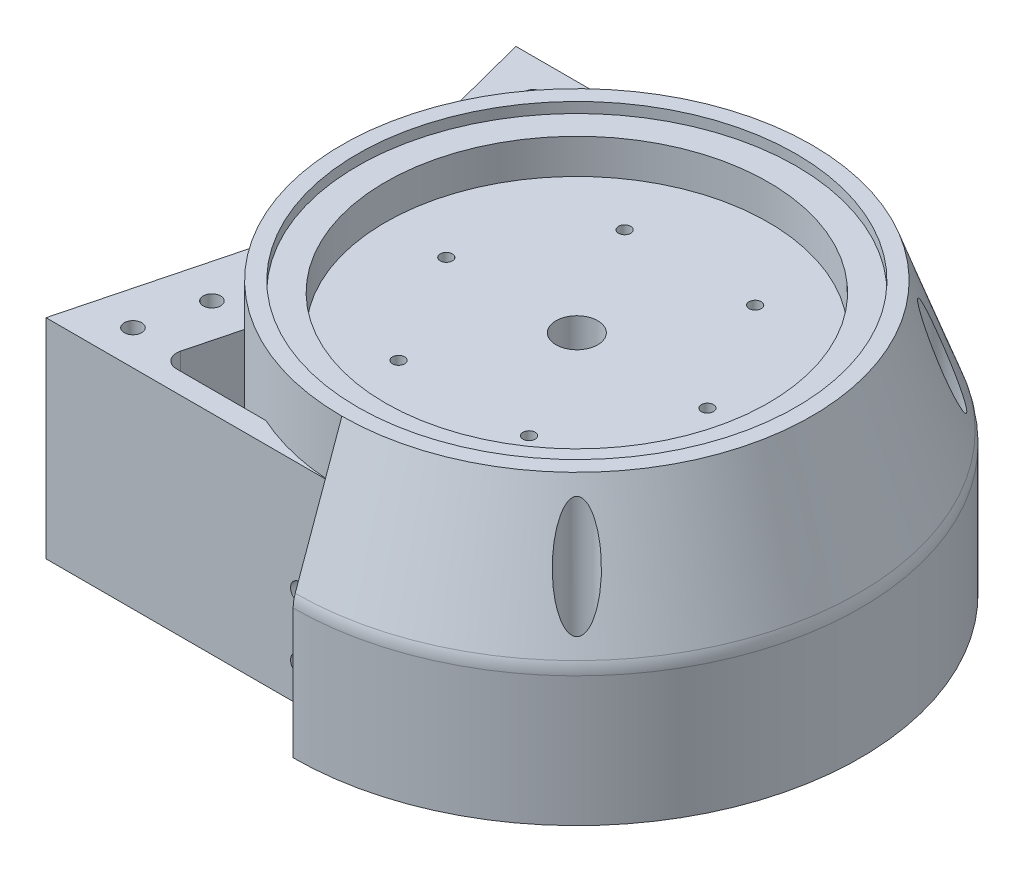
SolidWorks part; units mm, degrees
ref_plane "Alzado" through (0, 0, 0) normal (0, 0, 1) x (1, 0, 0)
ref_plane "Planta" through (0, 0, 0) normal (0, 1, 0) x (1, 0, 0)
ref_plane "Vista lateral" through (0, 0, 0) normal (1, 0, 0) x (0, 0, -1)
sketch "Croquis1" plane through (0, 0, 0) normal (0, 1, 0) x (1, 0, 0)
  line L0 (-55, 0) -> (55, 0) construction
  line L1 (-158, 67.5) -> (0, 67.5)
  line L2 (-158, 67.5) -> (-158, -67.5)
  line L3 (-158, -67.5) -> (0, -67.5)
  line L5 (-158, 67.5) -> (0, -67.5) construction
  line L6 (-158, -67.5) -> (0, 67.5) construction
  line L8 (-58.5, 0) -> (-48.5, 0) construction
  line L9 (-58.5, 0) -> (-48.5, 0) construction
  line L10 (-150, 59.5) -> (-93, 59.5) construction
  line L11 (-150, 59.5) -> (-150, 2.5) construction
  line L12 (-150, 2.5) -> (-93, 2.5) construction
  line L13 (-93, 59.5) -> (-93, 2.5) construction
  arc A0 (0, -67.5) -> (0, 67.5) centre (0, 0) ccw
  circle A1 centre (0, 0) radius 48.5 construction
  circle A2 centre (-71, 0) radius 12.5 construction
  point P4 (-79, 0)
  dimension "D1" = 135
  dimension "D2" = 97
  dimension "D3" = 25
  dimension "D4" = 10
  dimension "D5" = 8
  dimension "D6" = 57
  dimension "D7" = 8
  dimension "D8" = 158
extrude "Saliente-Extruir1" add sketch "Croquis1" along normal blind 110
sketch "Croquis2" plane through (0, 110, 0) normal (0, 1, 0) x (1, 0, 0)
  line L0 (-158, 67.5) -> (-158, -67.5) construction
  line L1 (-140, 59.5) -> (-103, 59.5)
  line L2 (-150, 49.5) -> (-150, 12.5)
  line L3 (-150, 12.5) -> (-140, 12.5)
  line L4 (-93, 49.5) -> (-93, 12.5)
  line L5 (0, 67.5) -> (-158, 67.5) construction
  line L6 (-150, 49.5) -> (-140, 49.5)
  line L7 (-140, 49.5) -> (-140, 59.5)
  line L8 (-121.5, 59.5) -> (-121.5, 2.5) construction
  line L9 (-150, 31) -> (-93, 31) construction
  line L10 (-103, 49.5) -> (-103, 59.5)
  line L11 (-93, 49.5) -> (-103, 49.5)
  line L12 (-93, 12.5) -> (-103, 12.5)
  line L13 (-103, 12.5) -> (-103, 2.5)
  line L14 (-140, 12.5) -> (-140, 2.5)
  line L16 (-140, 2.5) -> (-103, 2.5)
  point P13 (-121.5, 31)
  dimension "D1" = 8
  dimension "D2" = 8
  dimension "D3" = 37
  dimension "D4" = 37
  dimension "D5" = 57
extrude "Cortar-Extruir1" cut sketch "Croquis2" against normal blind 102
fillet "Redondeo1" radius 2 8 edges at (-150, 59, -49.5) (-150, 59, -12.5) (-140, 59, -2.5) (-103, 59, -2.5) (-93, 59, -12.5) (-93, 59, -49.5) (-103, 59, -59.5) (-140, 59, -59.5)
fillet "Redondeo2" radius 5 4 edges at (-103, 59, -12.5) (-140, 59, -12.5) (-103, 59, -49.5) (-140, 59, -49.5)
sketch "Croquis3" plane through (0, 110, 0) normal (0, 1, 0) x (1, 0, 0)
  line L0 (-150, 47.5) -> (-150, 14.5) construction
  line L1 (-150, 2.5) -> (-93, 2.5)
  line L2 (-150, 2.5) -> (-150, 59.5)
  line L3 (-150, 59.5) -> (-93, 59.5)
  line L4 (-93, 2.5) -> (-93, 59.5)
  line L5 (-138, 2.5) -> (-105, 2.5) construction
  line L6 (-105, 59.5) -> (-138, 59.5) construction
  line L7 (-93, 14.5) -> (-93, 47.5) construction
extrude "Cortar-Extruir2" cut sketch "Croquis3" against normal blind 5
sketch "Croquis4" plane through (0, 110, 0) normal (0, 1, 0) x (1, 0, 0)
  circle A0 centre (0, 0) radius 6
  dimension "D1" = 12
extrude "Cortar-Extruir3" cut sketch "Croquis4" against normal blind 100
sketch "Croquis5" plane through (0, 110, 0) normal (0, 1, 0) x (1, 0, 0)
  line L0 (-60.5, 0) -> (60.5, 0) construction
  line L1 (-89, -1000) -> (-89, 49000) construction
  line L2 (-93, 14.5) -> (-93, 47.5) construction
  circle A1 centre (-76.5, 0) radius 12.5 construction
  circle A2 centre (-76.5, 0) radius 3
  circle A3 centre (0, 0) radius 62 construction
  dimension "D1" = 124
  dimension "D2" = 25
  dimension "D4" = 6
  dimension "D3" = 4
extrude "Cortar-Extruir4" cut sketch "Croquis5" against normal blind 100
sketch "Croquis6" plane through (0, 110, 0) normal (0, 1, 0) x (1, 0, 0)
  line L0 (-68.1506, 2.5096) -> (-85, 67.5)
  line L1 (0, 67.5) -> (-158, 67.5) construction
  line L2 (-85, 67.5) -> (0, 67.5)
  line L3 (-60.5, 0) -> (60.5, 0) construction
  line L4 (-85, -67.5) -> (0, -67.5)
  line L5 (-68.1506, -2.5096) -> (-85, -67.5)
  line L6 (-93, 2.5) -> (-93, 59.5) construction
  arc A0 (0, -67.5) -> (0, 67.5) centre (0, 0) ccw
  arc A1 (0, -67.5) -> (0, 67.5) centre (0, 0) ccw construction
  arc A2 (-68.1506, 2.5096) -> (-68.1506, -2.5096) centre (-77.8306, 0) cw
  point P20 (-67.5, 0)
  dimension "D2" = 10
  dimension "D1" = 8
extrude "Cortar-Extruir5" cut sketch "Croquis6" against normal blind 32
sketch "Croquis7" plane through (0, 110, 0) normal (0, 1, 0) x (1, 0, 0)
  line L0 (-70.8172, -12.7947) -> (-85, -67.5)
  line L1 (-68.1506, -2.5096) -> (-85, -67.5) construction
  line L2 (-85, -67.5) -> (-158, -67.5)
  line L3 (-93, 2.5) -> (-158, 2.5)
  line L4 (-158, 67.5) -> (-158, -67.5) construction
  line L5 (-158, 2.5) -> (-158, -67.5)
  line L6 (-138, 2.5) -> (-105, 2.5) construction
  line L7 (-93, 2.5) -> (-89.2537, -5.7744)
  arc A0 (-89.2537, -5.7744) -> (-70.8172, -12.7947) centre (-76.5, 0) ccw
  dimension "D1" = 28
extrude "Saliente-Extruir2" add sketch "Croquis7" along normal blind 23
sketch "Croquis8" plane through (0, 133, 0) normal (0, 1, 0) x (1, 0, 0)
  line L0 (-158, 0) -> (-93, 0) construction
  line L1 (-158, 2.5) -> (-158, -67.5) construction
  line L2 (-105, -59.5) -> (-138, -59.5)
  line L3 (-103, -54.5) -> (-103, -57.5)
  line L4 (-95, -49.5) -> (-98, -49.5)
  line L5 (-93, -14.5) -> (-93, -47.5)
  line L6 (-98, -12.5) -> (-95, -12.5)
  line L7 (-103, -4.5) -> (-103, -7.5)
  line L8 (-138, -2.5) -> (-105, -2.5)
  line L9 (-140, -7.5) -> (-140, -4.5)
  line L10 (-148, -12.5) -> (-145, -12.5)
  line L11 (-150, -47.5) -> (-150, -14.5)
  line L12 (-145, -49.5) -> (-148, -49.5)
  line L13 (-140, 57.5) -> (-140, 54.5)
  line L14 (-145, 49.5) -> (-148, 49.5)
  line L15 (-150, 47.5) -> (-150, 14.5)
  line L16 (-148, 12.5) -> (-145, 12.5)
  line L17 (-140, 7.5) -> (-140, 4.5)
  line L18 (-138, 2.5) -> (-105, 2.5)
  line L19 (-103, 4.5) -> (-103, 7.5)
  line L20 (-98, 12.5) -> (-95, 12.5)
  line L21 (-93, 14.5) -> (-93, 47.5)
  line L22 (-95, 49.5) -> (-98, 49.5)
  line L23 (-103, 54.5) -> (-103, 57.5)
  line L24 (-105, 59.5) -> (-138, 59.5)
  line L25 (-140, 57.5) -> (-140, 54.5) construction
  line L26 (-145, 49.5) -> (-148, 49.5) construction
  line L27 (-150, 47.5) -> (-150, 14.5) construction
  line L28 (-148, 12.5) -> (-145, 12.5) construction
  line L29 (-140, 7.5) -> (-140, 4.5) construction
  line L30 (-138, 2.5) -> (-105, 2.5) construction
  line L31 (-103, 4.5) -> (-103, 7.5) construction
  line L32 (-98, 12.5) -> (-95, 12.5) construction
  line L33 (-93, 14.5) -> (-93, 47.5) construction
  line L34 (-95, 49.5) -> (-98, 49.5) construction
  line L35 (-103, 54.5) -> (-103, 57.5) construction
  line L36 (-105, 59.5) -> (-138, 59.5) construction
  line L37 (-140, -57.5) -> (-140, -54.5)
  line L38 (-158, -67.5) -> (-85, -67.5) construction
  arc A0 (-138, -59.5) -> (-140, -57.5) centre (-138, -57.5) cw
  arc A1 (-103, -57.5) -> (-105, -59.5) centre (-105, -57.5) cw
  arc A2 (-103, -54.5) -> (-98, -49.5) centre (-98, -54.5) cw
  arc A3 (-93, -47.5) -> (-95, -49.5) centre (-95, -47.5) cw
  arc A4 (-95, -12.5) -> (-93, -14.5) centre (-95, -14.5) cw
  arc A5 (-98, -12.5) -> (-103, -7.5) centre (-98, -7.5) cw
  arc A6 (-105, -2.5) -> (-103, -4.5) centre (-105, -4.5) cw
  arc A7 (-140, -4.5) -> (-138, -2.5) centre (-138, -4.5) cw
  arc A8 (-140, -7.5) -> (-145, -12.5) centre (-145, -7.5) cw
  arc A9 (-150, -14.5) -> (-148, -12.5) centre (-148, -14.5) cw
  arc A10 (-148, -49.5) -> (-150, -47.5) centre (-148, -47.5) cw
  arc A11 (-145, -49.5) -> (-140, -54.5) centre (-145, -54.5) cw
  arc A12 (-145, 49.5) -> (-140, 54.5) centre (-145, 54.5) ccw
  arc A13 (-148, 49.5) -> (-150, 47.5) centre (-148, 47.5) ccw
  arc A14 (-150, 14.5) -> (-148, 12.5) centre (-148, 14.5) ccw
  arc A15 (-140, 7.5) -> (-145, 12.5) centre (-145, 7.5) ccw
  arc A16 (-140, 4.5) -> (-138, 2.5) centre (-138, 4.5) ccw
  arc A17 (-105, 2.5) -> (-103, 4.5) centre (-105, 4.5) ccw
  arc A18 (-98, 12.5) -> (-103, 7.5) centre (-98, 7.5) ccw
  arc A19 (-95, 12.5) -> (-93, 14.5) centre (-95, 14.5) ccw
  arc A20 (-93, 47.5) -> (-95, 49.5) centre (-95, 47.5) ccw
  arc A21 (-103, 54.5) -> (-98, 49.5) centre (-98, 54.5) ccw
  arc A22 (-103, 57.5) -> (-105, 59.5) centre (-105, 57.5) ccw
  arc A23 (-138, 59.5) -> (-140, 57.5) centre (-138, 57.5) ccw
  arc A24 (-145, 49.5) -> (-140, 54.5) centre (-145, 54.5) ccw construction
  arc A25 (-148, 49.5) -> (-150, 47.5) centre (-148, 47.5) ccw construction
  arc A26 (-150, 14.5) -> (-148, 12.5) centre (-148, 14.5) ccw construction
  arc A27 (-140, 7.5) -> (-145, 12.5) centre (-145, 7.5) ccw construction
  arc A28 (-140, 4.5) -> (-138, 2.5) centre (-138, 4.5) ccw construction
  arc A29 (-105, 2.5) -> (-103, 4.5) centre (-105, 4.5) ccw construction
  arc A30 (-98, 12.5) -> (-103, 7.5) centre (-98, 7.5) ccw construction
  arc A31 (-95, 12.5) -> (-93, 14.5) centre (-95, 14.5) ccw construction
  arc A32 (-93, 47.5) -> (-95, 49.5) centre (-95, 47.5) ccw construction
  arc A33 (-103, 54.5) -> (-98, 49.5) centre (-98, 54.5) ccw construction
  arc A34 (-103, 57.5) -> (-105, 59.5) centre (-105, 57.5) ccw construction
  arc A35 (-138, 59.5) -> (-140, 57.5) centre (-138, 57.5) ccw construction
  dimension "D2" = 8
  dimension "D1" = 0
extrude "Cortar-Extruir6" cut sketch "Croquis8" against normal blind 102
sketch "Croquis10" plane through (0, 133, 0) normal (0, 1, 0) x (1, 0, 0)
  line L0 (-150, -14.5) -> (-150, -47.5) construction
  line L1 (-150, -2.5) -> (-93, -2.5)
  line L2 (-150, -2.5) -> (-150, -59.5)
  line L3 (-150, -59.5) -> (-93, -59.5)
  line L4 (-93, -2.5) -> (-93, -59.5)
  line L5 (-105, -2.5) -> (-138, -2.5) construction
  line L6 (-93, -47.5) -> (-93, -14.5) construction
  line L7 (-138, -59.5) -> (-105, -59.5) construction
extrude "Cortar-Extruir7" cut sketch "Croquis10" against normal blind 5
sketch "Croquis11" plane through (0, 78, 0) normal (0, 1, 0) x (1, 0, 0)
  line L1 (0, 0) -> (-63, 0) construction
  circle A0 centre (0, 0) radius 63
  circle A1 centre (0, 0) radius 45 construction
  dimension "D1" = 126
  dimension "D2" = 90
extrude "Cortar-Extruir8" cut sketch "Croquis11" against normal blind 3 and the other way through all
sketch "Croquis12" plane through (0, 78, 0) normal (0, 1, 0) x (1, 0, 0)
  circle A0 centre (0, 0) radius 55
  dimension "D1" = 110
extrude "Cortar-Extruir9" cut sketch "Croquis12" against normal blind 13
sketch "Croquis13" plane through (0, 65, 0) normal (0, 1, 0) x (1, 0, 0)
  circle A0 centre (0, 0) radius 37.5 construction
  circle A1 centre (-37.5, 0) radius 1.5
  dimension "D1" = 75
  dimension "D2" = 3
extrude "Cortar-Extruir10" cut sketch "Croquis13" against normal blind 14
sketch "Croquis14" plane through (0, 65, 0) normal (0, 1, 0) x (1, 0, 0)
  circle A0 centre (-37.5, 0) radius 1.75
  dimension "D1" = 3.5
extrude "Cortar-Extruir11" cut sketch "Croquis14" against normal blind 6
pattern_circular "MatrizC1" count 6 over 360 about axis through (0, 65, 0) along (0, 1, 0) of "Cortar-Extruir11", "Cortar-Extruir10"
sketch "Croquis16" plane through (0, 110, 0) normal (0, 1, 0) x (1, 0, 0)
  circle A0 centre (-98, 7.5) radius 2.75 construction
  circle A1 centre (-145, 7.5) radius 2.75 construction
  circle A2 centre (-98, 54.5) radius 2.75 construction
  circle A3 centre (-145, 54.5) radius 2.75 construction
  circle A4 centre (-98, 7.5) radius 2.75
  circle A5 centre (-145, 7.5) radius 2.75
  circle A6 centre (-98, 54.5) radius 2.75
  circle A7 centre (-145, 54.5) radius 2.75
sketch "Croquis17" plane through (0, 133, 0) normal (0, 1, 0) x (1, 0, 0)
  circle A0 centre (-145, -54.5) radius 2.75 construction
  circle A1 centre (-98, -54.5) radius 2.75 construction
  circle A2 centre (-98, -7.5) radius 2.75 construction
  circle A3 centre (-145, -7.5) radius 2.75 construction
  circle A4 centre (-145, -54.5) radius 2.75
  circle A5 centre (-98, -54.5) radius 2.75
  circle A6 centre (-98, -7.5) radius 2.75
  circle A7 centre (-145, -7.5) radius 2.75
ref_plane "Plano1" through (0, 39, 0) normal (0, -1, 0) x (-1, 0, 0)
extrude "Cortar-Extruir12" cut sketch "Croquis17" against normal blind 30
sketch "Croquis18" plane through (0, 128, 0) normal (0, 1, 0) x (1, 0, 0)
  circle A0 centre (-145, -7.5) radius 3.35
  circle A1 centre (-98, -7.5) radius 3.35
  circle A2 centre (-98, -54.5) radius 3.35
  circle A3 centre (-145, -54.5) radius 3.35
  dimension "D1" = 6.7
extrude "Cortar-Extruir13" cut sketch "Croquis18" against normal blind 5
extrude "Cortar-Extruir14" cut sketch "Croquis16" against normal blind 30
sketch "Croquis19" plane through (0, 105, 0) normal (0, 1, 0) x (1, 0, 0)
  circle A0 centre (-145, 54.5) radius 3.35
  circle A1 centre (-98, 54.5) radius 3.35
  circle A2 centre (-145, 7.5) radius 3.35
  circle A3 centre (-98, 7.5) radius 3.35
  dimension "D1" = 6.7
extrude "Cortar-Extruir15" cut sketch "Croquis19" against normal blind 5
sketch "Croquis20" plane through (0, 0, 0) normal (0, -1, 0) x (1, 0, 0)
  line L0 (0, -67.5) -> (-158, -67.5) construction
  line L1 (-158, 67.5) -> (0, 67.5) construction
  line L2 (0, -67.5) -> (-158, -67.5)
  line L3 (-158, 67.5) -> (0, 67.5)
  arc A0 (0, -67.5) -> (0, 67.5) centre (0, 0) ccw construction
  arc A1 (0, -67.5) -> (0, 67.5) centre (0, 0) ccw
sketch "Croquis21" plane through (-158, 0, 0) normal (1, 0, 0) x (0, 0, -1)
  line L0 (-67.5, 0) -> (67.5, 0) construction
  line L1 (-67.5, 0) -> (-81.5, 0)
  line L2 (-67.5, 0) -> (-67.5, 39)
  line L4 (-81.5, 0) -> (-81.5, 37.2595)
  line L5 (-89.65, 39) -> (89.65, 39) construction
  line L6 (-80.9119, 40.6381) -> (-67.5, 78)
  line L7 (-67.5, 78) -> (-67.5, 39)
  arc A0 (-80.9119, 40.6381) -> (-81.5, 37.2595) centre (-71.5, 37.2595) ccw
  point P12 (-81.5, 39)
  dimension "D2" = 10
  dimension "D1" = 14
sweep "Barrer1" add profiles "Croquis21" path "Croquis20"
sketch "Croquis22" plane through (0, 39, 0) normal (0, -1, 0) x (-1, 0, 0)
  line L0 (0, -74.206) -> (158, -74.206) construction
  line L1 (158, -67.5) -> (158, -80.9119) construction
  line L2 (0, 74.206) -> (158, 74.206) construction
  line L3 (158, 67.5) -> (158, 80.9119) construction
  line L4 (0, 0) -> (158, 0) construction
  line L5 (158, 2.5) -> (158, -67.5) construction
  line L6 (0, 0) -> (-52.4715, 52.4715) construction
  arc A0 (0, 74.206) -> (0, -74.206) centre (0, 0) ccw construction
  circle A1 centre (118.5, 74.206) radius 3
  circle A2 centre (39.5, 74.206) radius 3
  circle A3 centre (-52.4715, 52.4715) radius 3
  circle A4 centre (118.5, -74.206) radius 3
  circle A5 centre (39.5, -74.206) radius 3
  circle A6 centre (-52.4715, -52.4715) radius 3
  dimension "D1" = 79
  dimension "D2" = 39.5
  dimension "D3" = 6
  dimension "D4" = 45
extrude "Cortar-Extruir16" cut sketch "Croquis22" against normal through all both and the other way through all
sketch "Croquis23" plane through (0, 0, 0) normal (0, 1, 0) x (1, 0, 0)
  line L0 (0, 0) -> (-158, 0) construction
  line L1 (-158, 2.5) -> (-158, -67.5) construction
  circle A0 centre (-118.5, 74.206) radius 5
  circle A1 centre (-39.5, 74.206) radius 5
  circle A2 centre (52.4715, 52.4715) radius 5
  circle A3 centre (52.4715, 52.4715) radius 3 construction
  circle A4 centre (52.4715, -52.4715) radius 5
  circle A5 centre (-39.5, -74.206) radius 5
  circle A6 centre (-118.5, -74.206) radius 5
  dimension "D1" = 10
extrude "Cortar-Extruir17" cut sketch "Croquis23" along normal through all from offset 30
sketch "Croquis25" plane through (0, 0, 0) normal (0, 1, 0) x (1, 0, 0)
  line L24 (-85, 67.5) -> (-68.1506, 2.5096) construction
  line L25 (-68.1506, -2.5096) -> (-85, -67.5) construction
  line L26 (-85, 67.5) -> (-68.1506, 2.5096)
  line L27 (-68.1506, -2.5096) -> (-85, -67.5)
  line L28 (0, 67.5) -> (-85, 67.5) construction
  line L29 (-85, -67.5) -> (0, -67.5) construction
  line L30 (0, 67.5) -> (-85, 67.5)
  line L31 (-85, -67.5) -> (0, -67.5)
  line L32 (0, 67.5) -> (0, 97.247)
  line L33 (0, -73.15) -> (0, 73.15) construction
  line L34 (0, -67.5) -> (0, -105.1206)
  arc A6 (-68.1506, -2.5096) -> (-68.1506, 2.5096) centre (-77.8306, 0) ccw construction
  arc A7 (-68.1506, -2.5096) -> (-68.1506, 2.5096) centre (-77.8306, 0) ccw
  spline S0 degree 3 poles (0, -105.1206) (-292.6015, -314.7844) (-275.6385, 323.1016) (0, 97.247) knots 0 0 0 0 1 1 1 1
extrude "Cortar-Extruir18" cut sketch "Croquis25" along normal through all
sketch "Croquis26" plane through (0, 0, 0) normal (0, 1, 0) x (1, 0, 0)
  arc A0 (0, 67.5) -> (0, -67.5) centre (0, 0) ccw
  arc A1 (0, -67.5) -> (0, 67.5) centre (0, 0) ccw construction
  spline S0 degree 3 poles (0, 67.5) (-181.92, 227.2875) (-171.3846, -221.3808) (0, -67.5) knots 0 0 0 0 1 1 1 1
extrude "Cortar-Extruir19" cut sketch "Croquis26" along normal through all from offset 60
sketch "Croquis28" plane through (0, 0, -67.5) normal (0, 0, -1) x (-1, 0, 0)
  line L0 (74.25, 0) -> (-74.25, 0) construction
  line L1 (0, 73.15) -> (0, -73.15) construction
  circle A0 centre (12, 10) radius 2.5
  circle A1 centre (12, 28) radius 2.5
  point P4 (0, 0)
  dimension "D1" = 5
  dimension "D2" = 10
  dimension "D3" = 18
  dimension "D4" = 12
extrude "Cortar-Extruir20" cut sketch "Croquis28" against normal blind 25
sketch "Croquis29" plane through (0, 0, -67.5) normal (0, 0, -1) x (-1, 0, 0)
  circle A0 centre (12, 28) radius 2.75
  circle A1 centre (12, 10) radius 2.75
  dimension "D1" = 5.5
extrude "Cortar-Extruir21" cut sketch "Croquis29" against normal blind 6.6
sketch "Croquis30" plane through (0, 60, 0) normal (0, 1, 0) x (1, 0, 0)
  line L0 (-72.6033, 67.5) -> (-62.014, 26.6555) construction
  line L1 (0, 67.5) -> (-85, 67.5) construction
  line L2 (-85, 67.5) -> (-68.1506, 2.5096) construction
  arc A0 (0, 67.5) -> (0, -67.5) centre (0, 0) ccw construction
  circle A1 centre (-70.0107, 57.5) radius 2.5
  circle A2 centre (-65.344, 39.5) radius 2.5
  dimension "D2" = 5
  dimension "D3" = 10
  dimension "D4" = 18
  dimension "D1" = 12
extrude "Cortar-Extruir22" cut sketch "Croquis30" against normal blind 45
sketch "Croquis31" plane through (0, 60, 0) normal (0, 1, 0) x (1, 0, 0)
  line L0 (-27.8209, 61.5) -> (-53.4817, 61.5)
  line L1 (-57.3537, 56.4962) -> (-53.4081, 41.2774)
  line L2 (-85, 67.5) -> (-68.1506, 2.5096) construction
  line L3 (0, 67.5) -> (-85, 67.5) construction
  arc A0 (0, 67.5) -> (0, -67.5) centre (0, 0) ccw construction
  arc A1 (-27.8209, 61.5) -> (-53.4081, 41.2774) centre (0, 0) ccw
  arc A2 (-53.4817, 61.5) -> (-57.3537, 56.4962) centre (-53.4817, 57.5) ccw
  dimension "D3" = 4
  dimension "D1" = 6
  dimension "D2" = 24
extrude "Cortar-Extruir23" cut sketch "Croquis31" against normal through all
sketch "Croquis32" plane through (0, 60, 0) normal (0, 1, 0) x (1, 0, 0)
  line L0 (-85, 67.5) -> (-68.1506, 2.5096) construction
  line L1 (-65.2764, 57.5) -> (-67.6435, 61.6)
  line L2 (-67.6435, 61.6) -> (-83.4704, 61.6)
  line L5 (-81.3444, 53.4) -> (-67.6435, 53.4)
  line L6 (-67.6435, 53.4) -> (-65.2764, 57.5)
  line L7 (-60.6097, 39.5) -> (-62.9769, 43.6)
  line L8 (-62.9769, 43.6) -> (-78.8037, 43.6)
  line L11 (-76.6778, 35.4) -> (-62.9769, 35.4)
  line L12 (-62.9769, 35.4) -> (-60.6097, 39.5)
  line L13 (-71.234, 41.5018) -> (-68.1236, 36.1143) [skipped]
  line L14 (-66.5554, 45.6018) -> (-69.6658, 40.2143) [skipped]
  line L15 (-78.8037, 43.6) -> (-76.6778, 35.4)
  line L16 (-83.4704, 61.6) -> (-81.3444, 53.4)
  line L17 (-70.8885, 64.1795) -> (-74.257, 58.3451) [skipped]
  line L18 (-76.2342, 60.0795) -> (-72.8657, 54.2451) [skipped]
  circle A0 centre (-70.0107, 57.5) radius 4.1 construction
  circle A1 centre (-65.344, 39.5) radius 4.1 construction
  dimension "D1" = 8.2
  dimension "D2" = 8.2
extrude "Cortar-Extruir24" cut sketch "Croquis32" against normal blind 4.2 from offset 25 offset against normal yes
sketch "Croquis33" plane through (-63.2487, 0, 16.3978) normal (-0.968, 0, 0.251) x (0.251, 0, 0.968)
  line L0 (-19.5325, 0) -> (-86.6716, 0) construction
  line L1 (-69.0817, 0) -> (-61.0817, 0)
  line L2 (-69.0817, 0) -> (-69.0817, 1)
  line L3 (-69.0817, 1) -> (-61.0817, 1)
  line L4 (-61.0817, 0) -> (-61.0817, 1)
  line L5 (-69.0817, 0) -> (-61.0817, 1) construction
  line L6 (-69.0817, 1) -> (-61.0817, 0) construction
  line L7 (-69.0817, 0) -> (-69.0817, 60) construction
  point P0 (-65.0817, 0.5)
  dimension "D1" = 1
  dimension "D2" = 8
extrude "Cortar-Extruir25" cut sketch "Croquis33" against normal up to next
fillet "Redondeo3" radius 1 2 edges at (-66.9619, 1, -45.7406) (-68.9696, 1, -53.4846)
ref_axis "Eje1" through (0, 10, 0) along (0, 1, 0)
ref_plane "Plano2" through (0, 0, 0) normal (0, 0, -1) x (0, 1, 0)
mirror "Simetría1" about plane through (0, 0, 0) normal (0, 0, -1) of "Redondeo3", "Cortar-Extruir25", "Cortar-Extruir24", "Cortar-Extruir23", "Cortar-Extruir22", "Cortar-Extruir21", "Cortar-Extruir20"
